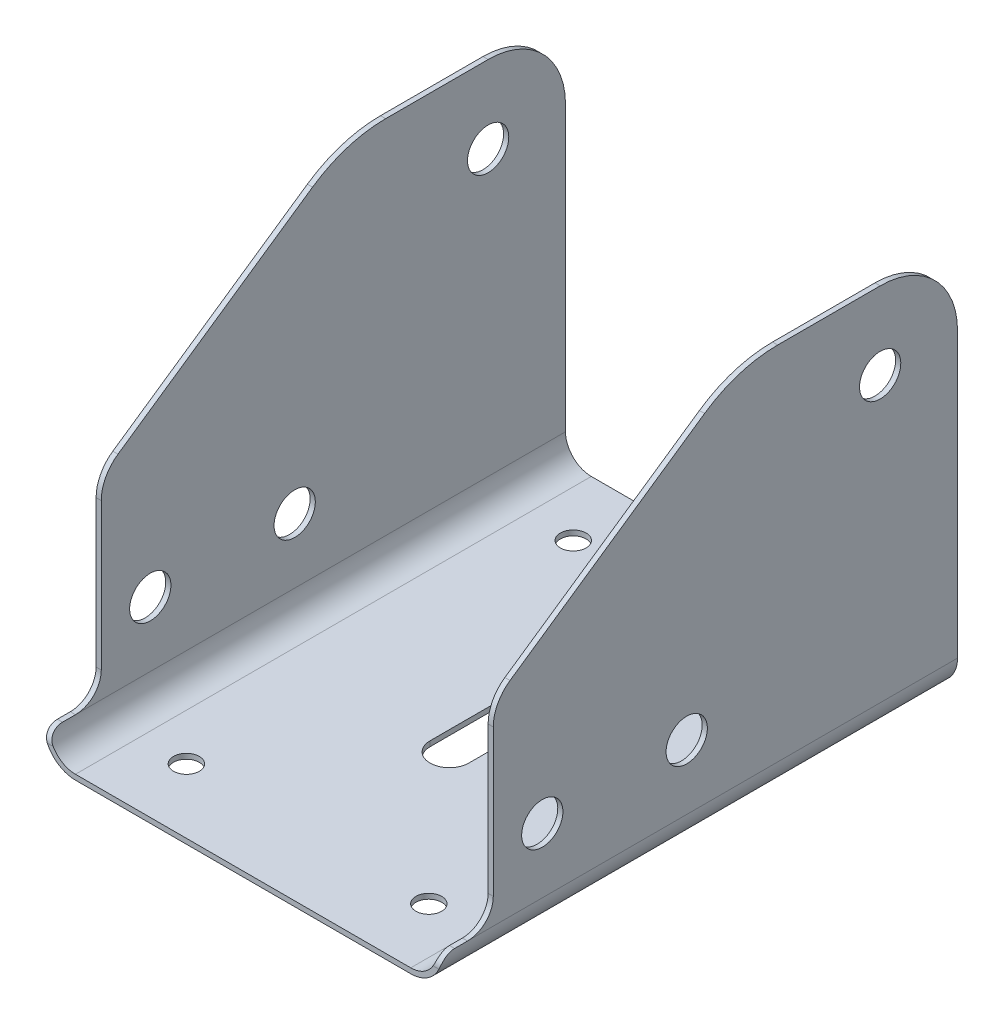
SolidWorks part; units mm, degrees
note: The reader was unsure of these and kept them because the rebuilt part matched: thickness of "Base-Flange1", "Edge-Flange1", "Sheet-Metal1", "Sheet-Metal2", "Sheet-Metal3", "Sheet-Metal4"; flange length of "Edge-Flange1".
ref_plane "Front Plane" through (0, 0, 0) normal (0, 0, 1) x (1, 0, 0)
ref_plane "Top Plane" through (0, 0, 0) normal (0, 1, 0) x (1, 0, 0)
ref_plane "Right Plane" through (0, 0, 0) normal (1, 0, 0) x (0, 0, -1)
sketch "Sketch1" plane through (0, 0, 0) normal (0, 1, 0) x (1, 0, 0)
  line L1 (-75, 100) -> (75, 100)
  line L2 (-75, 100) -> (-75, -100)
  line L3 (-75, -100) -> (75, -100)
  line L4 (75, 100) -> (75, -100)
  line L5 (-75, 100) -> (75, -100) construction
  line L6 (-75, -100) -> (75, 100) construction
  point P0 (0, 0)
  dimension "D1" = 200
  dimension "D2" = 150
base flange "Base-Flange1" sketch "Sketch1" thickness 2 reverse thickness direction no parameters "D1"=0.7366
edge flange "Edge-Flange1" sketch "Sketch13" flange profiles "Sketch13", "Sketch14" flange angle 90 flange length 150 flange position material outside bend radius 10 thickness 2 relief rectangular parameters "D6"=0, "D8"=1
sketch "Sketch13" plane through (75, 0, 0) normal (1, 0, 0) x (0, 0, -1)
  line L0 (-100, 0) -> (100, 0) construction
  line L1 (-100, 0) -> (100, 0)
  line L2 (-100, 0) -> (-100, 150)
  line L3 (-100, 150) -> (100, 150)
  line L4 (100, 150) -> (100, 0)
  dimension "D1" = 150
sketch "Sketch14" plane through (-75, 0, 0) normal (-1, 0, 0) x (0, 0, 1)
  line L0 (-100, 0) -> (100, 0) construction
  line L1 (-100, 0) -> (100, 0)
  line L2 (-100, 0) -> (-100, 150)
  line L3 (-100, 150) -> (100, 150)
  line L4 (100, 150) -> (100, 0)
  dimension "D1" = 150
bend "EdgeBend1" bend radius 10 bend angle 90 parameters "D5"=1
bend "EdgeBend2" bend radius 10 bend angle 90 parameters "D5"=2
sketch "Sketch15" plane through (-77, 0, 0) normal (-1, 0, 0) x (0, 0, 1)
  line L0 (-1.9165, 141.1807) -> (73.5072, 89.2432)
  line L1 (100, 150) -> (-100, 150) construction
  line L2 (-100, 99) -> (-100, 120)
  line L4 (90, 10) -> (95, 10)
  line L8 (-49, 150) -> (-30.274, 150)
  line L9 (-100, 99) -> (-100, -2)
  line L10 (-100, -2) -> (100, -2)
  line L11 (100, 71) -> (100, -2) construction
  line L12 (80, 76.889) -> (80, 20)
  line L13 (-70, 150) -> (-49, 150)
  line L14 (100, 5) -> (100, -2)
  arc A1 (-1.9165, 141.1807) -> (-30.274, 150) centre (-30.274, 100) ccw
  circle A2 centre (61, 35) radius 8
  circle A3 centre (-70, 120) radius 8
  circle A4 centre (5, 35) radius 8
  arc A5 (90, 10) -> (80, 20) centre (90, 20) cw
  arc A6 (80, 76.889) -> (73.5072, 89.2432) centre (65, 76.889) ccw
  arc A7 (100, 5) -> (95, 10) centre (95, 5) ccw
  arc A8 (-100, 120) -> (-70, 150) centre (-70, 120) cw
  point P18 (-14.7239, 150)
  point P27 (100, 10)
  point P34 (-100, 150)
  dimension "D5" = 50
  dimension "D6" = 95
  dimension "D7" = 39
  dimension "D8" = 37
  dimension "D9" = 37
  dimension "D10" = 16
  dimension "D11" = 16
  dimension "D12" = 30
  dimension "D13" = 30
  dimension "D15" = 10
  dimension "D4" = 15
  dimension "D17" = 5
  dimension "D18" = 30
  dimension "D2" = 145.448
  dimension "D3" = 101
  dimension "D14" = 20
  dimension "D16" = 91.5765
extrude "Cut-Extrude1" cut sketch "Sketch15" against normal through all flip side to cut
sketch "Sketch16" plane through (0, 0, 0) normal (0, 1, 0) x (1, 0, 0)
  line L0 (65, 100) -> (-65, 100) construction
  line L2 (0, 100) -> (0, -100) construction
  line L3 (-65, -100) -> (65, -100) construction
  line L4 (-77, 0) -> (75, 0) construction
  line L5 (-77, 30.274) -> (-77, 1.9165) construction
  line L6 (75, 30.274) -> (75, 1.9165) construction
  line L7 (0, 20) -> (0, -20) construction
  line L8 (7.5, 20) -> (7.5, -20)
  line L9 (-7.5, 20) -> (-7.5, -20)
  line L10 (-77, -90) -> (-77, 100) construction
  circle A2 centre (-47, 75) radius 5
  circle A5 centre (47, 75) radius 5
  circle A6 centre (47, -75) radius 5
  circle A7 centre (-47, -75) radius 5
  arc A8 (7.5, 20) -> (-7.5, 20) centre (0, 20) ccw
  arc A9 (-7.5, -20) -> (7.5, -20) centre (0, -20) ccw
  point P25 (0, 0)
  dimension "D1" = 10
  dimension "D2" = 25
  dimension "D3" = 30
  dimension "D4" = 15
  dimension "D5" = 40
extrude "Cut-Extrude2" cut sketch "Sketch16" against normal through all
sketch "Bend-Lines1" [suppressed] plane through (0, 0, 0) normal (0, 1, 0) x (1, 0, 0)
sketch "Bounding-Box1" [suppressed] plane through (0, 0, 0) normal (0, 1, 0) x (1, 0, 0)
sheet metal parameters "Sheet-Metal1" thickness 2 parameters "D1"=0.7366
flat pattern "Flat-Pattern1" [suppressed]
sketch "Bend-Lines2" plane through (0, 0, 0) normal (0, 1, 0) x (1, 0, 0)
sketch "Bounding-Box2" [suppressed] plane through (0, 0, 0) normal (0, 1, 0) x (1, 0, 0)
sheet metal parameters "Sheet-Metal2" thickness 2 parameters "D1"=0.7366, "D7"=1
flat pattern "Flat-Pattern1" [suppressed]
sketch "Bend-Lines2" plane through (0, 0, 0) normal (0, 1, 0) x (1, 0, 0)
sketch "Bounding-Box2" [suppressed] plane through (0, 0, 0) normal (0, 1, 0) x (1, 0, 0)
bend of the flat pattern "Flatten-<EdgeBend1>1"
bend of the flat pattern "Flatten-<EdgeBend2>1"
sheet metal parameters "Sheet-Metal3" thickness 2 parameters "D1"=0.7366, "D7"=1
flat pattern "Flat-Pattern1"
sketch "Bend-Lines2" plane through (0, 0, 0) normal (0, 1, 0) x (1, 0, 0)
  line L0 (-75.2346, 100) -> (-75.2346, -100) construction
  line L1 (75.2346, -100) -> (75.2346, 100) construction
  line L2 (-75.2346, 100) -> (-75.2346, -100) construction
  line L3 (75.2346, -100) -> (75.2346, 100) construction
sketch3d "Bounding-Box2" [suppressed]
  line L0 (-225.4692, -100, 0) -> (225.4692, -100, 0) construction
  line L1 (-225.4692, 100, 0) -> (225.4692, 100, 0) construction
  line L2 (-225.4692, -100, 0) -> (-225.4692, 100, 0) construction
  line L3 (225.4692, -100, 0) -> (225.4692, 100, 0) construction
bend of the flat pattern "Flatten-<EdgeBend1>1"
bend of the flat pattern "Flatten-<EdgeBend2>1"
sheet metal parameters "Sheet-Metal4" thickness 2 parameters "D1"=0.7366, "D7"=1
flat pattern "Flat-Pattern1"
sketch "Bend-Lines2" plane through (0, 0, 0) normal (0, 1, 0) x (1, 0, 0)
  line L0 (-73.6394, -100) -> (-73.6394, 100) construction
  line L1 (73.6394, -100) -> (73.6394, 100) construction
  line L2 (-73.6394, -100) -> (-73.6394, 100) construction
  line L3 (73.6394, -100) -> (73.6394, 100) construction
sketch3d "Bounding-Box2" [suppressed]
  line L0 (-222.2788, -100, 0) -> (222.2788, -100, 0) construction
  line L1 (-222.2788, 100, 0) -> (222.2788, 100, 0) construction
  line L2 (-222.2788, -100, 0) -> (-222.2788, 100, 0) construction
  line L3 (222.2788, -100, 0) -> (222.2788, 100, 0) construction
bend of the flat pattern "Flatten-<EdgeBend1>1"
bend of the flat pattern "Flatten-<EdgeBend2>1"
